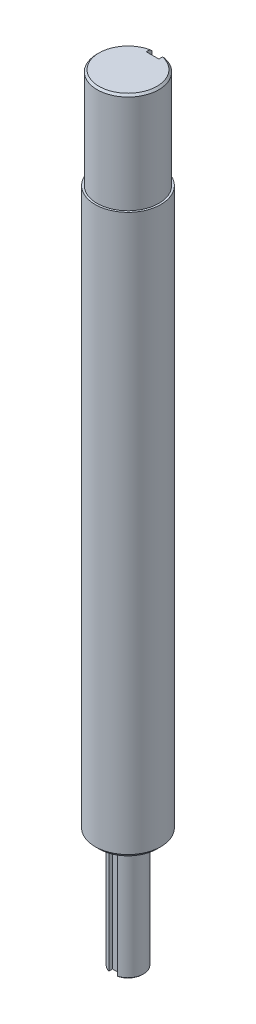
SolidWorks part; units mm, degrees
ref_plane "Front Plane" through (0, 0, 0) normal (0, 0, 1) x (1, 0, 0)
ref_plane "Top Plane" through (0, 0, 0) normal (0, 1, 0) x (1, 0, 0)
ref_plane "Right Plane" through (0, 0, 0) normal (1, 0, 0) x (0, 0, -1)
sketch "Sketch1" plane through (0, 0, 0) normal (0, 0, 1) x (1, 0, 0)
  line L1 (8.5, 201) -> (0, 201)
  line L2 (8.5, 201) -> (8.5, 0)
  line L3 (8.5, 0) -> (0, 0)
  line L4 (0, 201) -> (0, 0)
  line L5 (8.5, 201) -> (0, 0) construction
  line L6 (8.5, 0) -> (0, 201) construction
  point P0 (4.25, 100.5)
  dimension "D1" = 8.5
  dimension "D2" = 201
revolve "Revolve1" add sketch "Sketch1" angle 360 about L4
ref_axis "Axis1" through (0, 0, 0) along (0, 1, 0)
sketch "Sketch2" plane through (0, 201, 0) normal (0, 1, 0) x (1, 0, 0)
  circle A0 centre (0, 0) radius 8
  dimension "D1" = 16
extrude "Cut-Extrude1" cut sketch "Sketch2" against normal blind 26 flip side to cut
sketch "Sketch3" plane through (0, 201, 0) normal (0, 1, 0) x (1, 0, 0)
  line L1 (-1.625, 9.625) -> (1.625, 9.625)
  line L2 (-1.625, 9.625) -> (-1.625, 6.375)
  line L3 (-1.625, 6.375) -> (1.625, 6.375)
  line L4 (1.625, 9.625) -> (1.625, 6.375)
  line L5 (-1.625, 9.625) -> (1.625, 6.375) construction
  line L6 (-1.625, 6.375) -> (1.625, 9.625) construction
  circle A0 centre (0, 0) radius 8 construction
  point P0 (0, 8)
  dimension "D1" = 3.25
extrude "Cut-Extrude2" cut sketch "Sketch3" against normal up to surface (26 mm away) up to face at (-8, 175, 0)
chamfer "Chamfer1" distance 0.5 angle 45 2 edges at (-8.5, 0, 0) (0, 201, 8)
sketch "Sketch4" plane through (0, 0, 0) normal (0, -1, 0) x (1, 0, 0)
  circle A0 centre (0, 0) radius 4
  dimension "D1" = 8
extrude "Cut-Extrude3" cut sketch "Sketch4" against normal blind 30 flip side to cut
chamfer "Chamfer2" distance 1 angle 45 1 edges at (8.5, 30, 0)
sketch "Sketch5" plane through (0, 0, 0) normal (0, -1, 0) x (1, 0, 0)
  line L1 (-1.125, 5.125) -> (1.125, 5.125)
  line L2 (-1.125, 5.125) -> (-1.125, 2.875)
  line L3 (-1.125, 2.875) -> (1.125, 2.875)
  line L4 (1.125, 5.125) -> (1.125, 2.875)
  line L5 (-1.125, 5.125) -> (1.125, 2.875) construction
  line L6 (-1.125, 2.875) -> (1.125, 5.125) construction
  circle A1 centre (0, 0) radius 4 construction
  circle A2 centre (0, 0) radius 4 construction
  point P0 (0, 4)
  dimension "D1" = 2.25
extrude "Cut-Extrude4" cut sketch "Sketch5" against normal up to surface (30 mm away) up to face at (7.5, 30, 0)
chamfer "Chamfer3" distance 0.2 angle 45 4 edges at (-1.125, 0, 3.3568) (0, 0, 2.875) (1.125, 0, 3.3568) (0, 0, -4)
